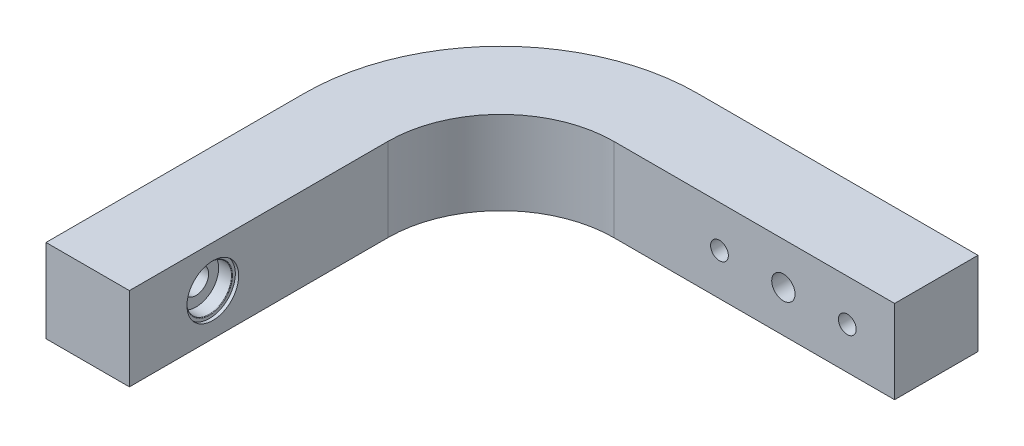
SolidWorks part; units mm, degrees
ref_plane "Front Plane" through (0, 0, 0) normal (0, 0, 1) x (1, 0, 0)
ref_plane "Top Plane" through (0, 0, 0) normal (0, 1, 0) x (1, 0, 0)
ref_plane "Right Plane" through (0, 0, 0) normal (1, 0, 0) x (0, 0, -1)
ref_axis "Z" through (0, 0, -59.2654) along (0, 0, 1)
sketch "Sketch1" plane through (0, 0, 0) normal (0, 1, 0) x (1, 0, 0)
  line L0 (-30.4827, 0) -> (30.4827, 0) construction
  line L1 (-65.8046, -35.3218) -> (-65.8046, -81.8046)
  line L2 (-65.8046, -81.8046) -> (-50.8046, -81.8046)
  line L3 (-50.8046, -81.8046) -> (-50.8046, -35.3218)
  line L4 (-30.4827, -15) -> (30.4827, -15) construction
  line L5 (0, -15) -> (0, 0) construction
  line L6 (50.8046, -81.8046) -> (50.8046, -35.3218) construction
  line L7 (65.8046, -81.8046) -> (50.8046, -81.8046) construction
  line L8 (65.8046, -35.3218) -> (65.8046, -81.8046) construction
  line L9 (30.4827, 0) -> (30.4827, -15) construction
  line L10 (20, -15) -> (20, 0)
  line L11 (-30.4827, -15) -> (20, -15)
  line L12 (-30.4827, 0) -> (20, 0)
  line L13 (0, 59.2654) -> (0, -30.9346) construction
  arc A0 (-30.4827, 0) -> (-65.8046, -35.3218) centre (-30.4827, -35.3218) ccw
  arc A1 (-50.8046, -35.3218) -> (-30.4827, -15) centre (-30.4827, -35.3218) cw
  arc A2 (50.8046, -35.3218) -> (30.4827, -15) centre (30.4827, -35.3218) ccw construction
  arc A3 (30.4827, 0) -> (65.8046, -35.3218) centre (30.4827, -35.3218) cw construction
  dimension "D3" = 20.3218
  dimension "D1" = 101.6092
  dimension "D2" = 15
  dimension "D4" = 66.8046
  dimension "D5" = 20
extrude "Boss-Extrude1" add sketch "Sketch1" along normal blind 7.5 and the other way blind 7.5
sketch "Sketch2" plane through (-50.8046, 0, 0) normal (-1, 0, 0) x (0, 0, 1)
  line L1 (44.9925, 0) -> (-44.9925, 0) construction
  line L2 (0, -8.25) -> (0, 8.25) construction
  circle A0 centre (66.8046, 0) radius 2.25
  dimension "D1" = 4.5
  dimension "D2" = 66.8046
extrude "Cut-Extrude1" cut sketch "Sketch2" against normal through all both and the other way through all
ref_axis "Axis2" through (-85.4136, 0, 66.8046) along (1, 0, 0)
sketch "Sketch3" plane through (0, 0, 0) normal (0, 0, -1) x (-1, 0, 0)
  line L0 (-11.5, 0) -> (11.5, 0) construction
  circle A0 centre (0, 0) radius 2.1
  circle A1 centre (-11.5, 0) radius 1.6
  circle A2 centre (11.5, 0) radius 1.6
  dimension "D1" = 4.2
  dimension "D3" = 3.2
  dimension "D2" = 23
extrude "Cut-Extrude2" cut sketch "Sketch3" against normal through all
sketch "Sketch5" plane through (0, 0, 0) normal (0, 1, 0) x (1, 0, 0)
  line L0 (-65.8046, -71.4546) -> (-65.2046, -71.4546)
  line L1 (-65.2046, -71.4546) -> (-65.2046, -70.9546)
  line L2 (-65.1046, -70.8546) -> (-62.8046, -70.8546)
  line L3 (-62.8046, -70.8546) -> (-62.8046, -66.8046)
  line L4 (-65.8046, -71.4546) -> (-65.8046, -66.8046)
  line L5 (-85.4136, -66.8046) -> (-36.6951, -66.8046) construction
  line L6 (-84.3923, -66.8046) -> (-79.5242, -66.8046) construction
  line L7 (-65.8046, -66.8046) -> (-62.8046, -66.8046)
  line L9 (-65.8046, -35.3218) -> (-65.8046, -81.8046) construction
  line L10 (-58.3046, -77.8481) -> (-58.3046, -69.6196) construction
  line L11 (-65.8046, -81.8046) -> (-50.8046, -81.8046) construction
  line L12 (-50.8046, -66.8046) -> (-53.8046, -66.8046)
  line L13 (-50.8046, -71.4546) -> (-50.8046, -66.8046)
  line L14 (-53.8046, -70.8546) -> (-53.8046, -66.8046)
  line L15 (-51.5046, -70.8546) -> (-53.8046, -70.8546)
  line L16 (-51.4046, -71.4546) -> (-51.4046, -70.9546)
  line L17 (-50.8046, -71.4546) -> (-51.4046, -71.4546)
  arc A0 (-65.1046, -70.8546) -> (-65.2046, -70.9546) centre (-65.1046, -70.9546) ccw
  arc A1 (-51.5046, -70.8546) -> (-51.4046, -70.9546) centre (-51.5046, -70.9546) cw
  point P14 (-58.3046, -81.8046)
  point P25 (-65.2046, -70.8546)
  point P28 (-51.4046, -70.8546)
  dimension "D5" = 0.1
  dimension "D6" = 0.1
  dimension "D1" = 0.6
  dimension "D2" = 4.65
  dimension "D3" = 8.1
  dimension "D4" = 3
revolve "bearing-seats" cut sketch "Sketch5" angle 360 about L6
equation "\"width\"= \"EyeDiameter\" + \"EyeClearance\""
equation "\"prongwidth\"= \"L2Thickness\""
equation "\"D2@Sketch1\"=\"prongwidth\""
equation "\"D3@Sketch1\"=\"width\"/5"
equation "\"pronglength\"= \"BasePlaneDistance\"'model implicitly adds clearance (of prongwidth) to the hole drilled at the baseplanedistance"
equation "\"D4@Sketch1\"=\"pronglength\""
equation "\"D1@Boss-Extrude1\"=\"prongwidth\"/2"
equation "\"D2@Boss-Extrude1\"=\"prongwidth\"/2"
equation "\"lbracket-plane-to-axis\"= \"BasePlaneDistance\""
equation "\"D2@Sketch2\"=\"lbracket-plane-to-axis\""
equation "\"EyeDiameter\" = 99.60916292"
equation "\"BasePlaneDistance\" = \"EyeDiameter\"/2+\"L2Thickness\"+\"EyeClearance\""
equation "\"EyeClearance\" = 2"
equation "\"D1@Sketch1\"=\"EyeDiameter\"+\"EyeClearance\""
equation "\"BearingDepth\"= 6"
equation "\"BearingHousingID\"=4.5"
equation "\"BearingFlangeThickness\"= 0.75"
equation "\"BearingFlangeOD\"=7.5"
equation "\"PrinterFilamentThickness\"= 0.1"
equation "\"ApplyPrinterOffset\"= 1'if 1, adjust hole sizes to try and make pressfits work with the 3d printer"
equation "\"L2Thickness\" = 3.75 * \"shaft_diameter\""
equation "\"L2_ID\" = 20"
equation "\"vx\" = 0"
equation "\"vy\" = 0"
equation "\"vz\" = 200"
equation "\"parametric_end\" = 1"
equation "\"Rw_3_xx\" = -(\"vz\")/sqr((\"vx\")^2 + (\"vz\")^2)"
equation "\"Rw_3_xy\" = 0"
equation "\"Rw_3_xz\" = (\"vx\")/sqr((\"vx\")^2 + (\"vz\")^2)"
equation "\"Rw_3_zx\" = (\"vx\")/sqr((\"vx\")^2 + (\"vy\")^2 + (\"vz\")^2)"
equation "\"Rw_3_zy\" = (\"vy\")/sqr((\"vx\")^2 + (\"vy\")^2 + (\"vz\")^2)"
equation "\"Rw_3_zz\" = (\"vz\")/sqr((\"vx\")^2 + (\"vy\")^2 + (\"vz\")^2)"
equation "\"Rw_3_yx\" = (\"vx\")*(\"vy\")/sqr((\"vx\")^4 + (\"vx\")^2*(\"vy\")^2 + 2*(\"vx\")^2*(\"vz\")^2 + (\"vy\")^2*(\"vz\")^2 + (\"vz\")^4)"
equation "\"Rw_3_yy\" = -sqr((\"vx\")^2 + (\"vz\")^2)/sqr((\"vx\")^2 + (\"vy\")^2 + (\"vz\")^2)"
equation "\"Rw_3_yz\" = (\"vy\")*(\"vz\")/sqr((\"vx\")^4 + (\"vx\")^2*(\"vy\")^2 + 2*(\"vx\")^2*(\"vz\")^2 + (\"vy\")^2*(\"vz\")^2 + (\"vz\")^4)"
equation "\"O2Targx\" = -\"BasePlaneDistance\"*(\"vx\")*(\"vy\")/sqr((\"vx\")^4 + (\"vx\")^2*(\"vy\")^2 + 2*(\"vx\")^2*(\"vz\")^2 + (\"vy\")^2*(\"vz\")^2 + (\"vz\")^4)"
equation "\"O2Targy\" = \"BasePlaneDistance\"*sqr((\"vx\")^2 + (\"vz\")^2)/sqr((\"vx\")^2 + (\"vy\")^2 + (\"vz\")^2)"
equation "\"O2Targz\" = -\"BasePlaneDistance\"*(\"vy\")*(\"vz\")/sqr((\"vx\")^4 + (\"vx\")^2*(\"vy\")^2 + 2*(\"vx\")^2*(\"vz\")^2 + (\"vy\")^2*(\"vz\")^2 + (\"vz\")^4)"
equation "\"O2Targx_0\" = -(\"BasePlaneDistance\")*sqr((\"vx\")^2 + (\"vz\")^2)/sqr((\"vx\")^2 + (\"vy\")^2 + (\"vz\")^2)"
equation "\"O2Targy_0\" = -(\"BasePlaneDistance\")*(\"vy\")*(\"vz\")/sqr((\"vx\")^4 + (\"vx\")^2*(\"vy\")^2 + 2*(\"vx\")^2*(\"vz\")^2 + (\"vy\")^2*(\"vz\")^2 + (\"vz\")^4)"
equation "\"O2Targz_0\" = (\"BasePlaneDistance\")*(\"vx\")*(\"vy\")/sqr((\"vx\")^4 + (\"vx\")^2*(\"vy\")^2 + 2*(\"vx\")^2*(\"vz\")^2 + (\"vy\")^2*(\"vz\")^2 + (\"vz\")^4) + (\"BasePlaneDistance\")"
equation "\"theta2_s1\" = arcsin(((\"BasePlaneDistance\") - (\"O2Targz_0\"))/(\"BasePlaneDistance\")) + pi"
equation "\"theta2_s2\" = -arcsin(((\"BasePlaneDistance\") - (\"O2Targz_0\"))/(\"BasePlaneDistance\"))"
equation "\"theta1_s1\" = arcsin((\"O2Targy_0\")/((\"BasePlaneDistance\")*cos((\"Theta2\")))) + pi"
equation "\"theta1_s2\" = -arcsin((\"O2Targy_0\")/((\"BasePlaneDistance\")*cos((\"Theta2\"))))"
equation "\"theta1_s3\" = -arccos(-(\"O2Targx_0\")/((\"BasePlaneDistance\")*cos((\"Theta2\")))) + 2*pi"
equation "\"theta1_s4\" = arccos(-(\"O2Targx_0\")/((\"BasePlaneDistance\")*cos((\"Theta2\"))))"
equation "\"Theta1\" = \"theta1_s2\" 'so far, theta1_s1 and theta1_s4 have agreed, and they agree with the sw constraint solver"
equation "\"Theta2\" = \"theta2_s2\""
equation "\"o2_x\" = -(\"BasePlaneDistance\")*cos((\"Theta1\"))*cos((\"Theta2\"))"
equation "\"o2_y\" = -(\"BasePlaneDistance\")*sin((\"Theta1\"))*cos((\"Theta2\"))"
equation "\"o2_z\" = (\"BasePlaneDistance\")*(sin((\"Theta2\")) + 1)"
equation "\"o1_x\" = (\"BasePlaneDistance\")*sin((\"Theta1\"))"
equation "\"o1_y\" = -(\"BasePlaneDistance\")*cos((\"Theta1\"))"
equation "\"o1_z\" = (\"BasePlaneDistance\")"
equation "\"Actuator1_Theta\" = atn(\"vx\"/\"vz\") 'ik solution for the single link joint"
equation "\"Actuator2_Theta\" = \"Theta1\"  'ik solution for the double link joint"
equation "\"MotorBaseThickness\" = 3 "
equation "\"BaseThickness\" = 3 "
equation "\"EncoderToMagnetAirgap\" = 1 'Encoder to magnet airgap"
equation "\"EncoderHeight\" = 1.192  'Height of the encoder"
equation "\"MagnetThickness\" = 0.5  'Magnet thickness"
equation "\"pcb_thickness\" = 1.6  'Thickness of the PCB"
equation "\"pcb_outer_diameter\" = 32 'the OD of the pcb"
equation "\"shaft_diameter\" = 4"
equation "\"D1@Sketch2\"=\"shaft_diameter\"*1.125"
equation "\"D2@Sketch5\"=\"ApplyPrinterOffset\" * \"PrinterFilamentThickness\" / 2 + 4.6"
equation "\"D3@Sketch5\"= \"ApplyPrinterOffset\" * \"PrinterFilamentThickness\"  + 8.00"
